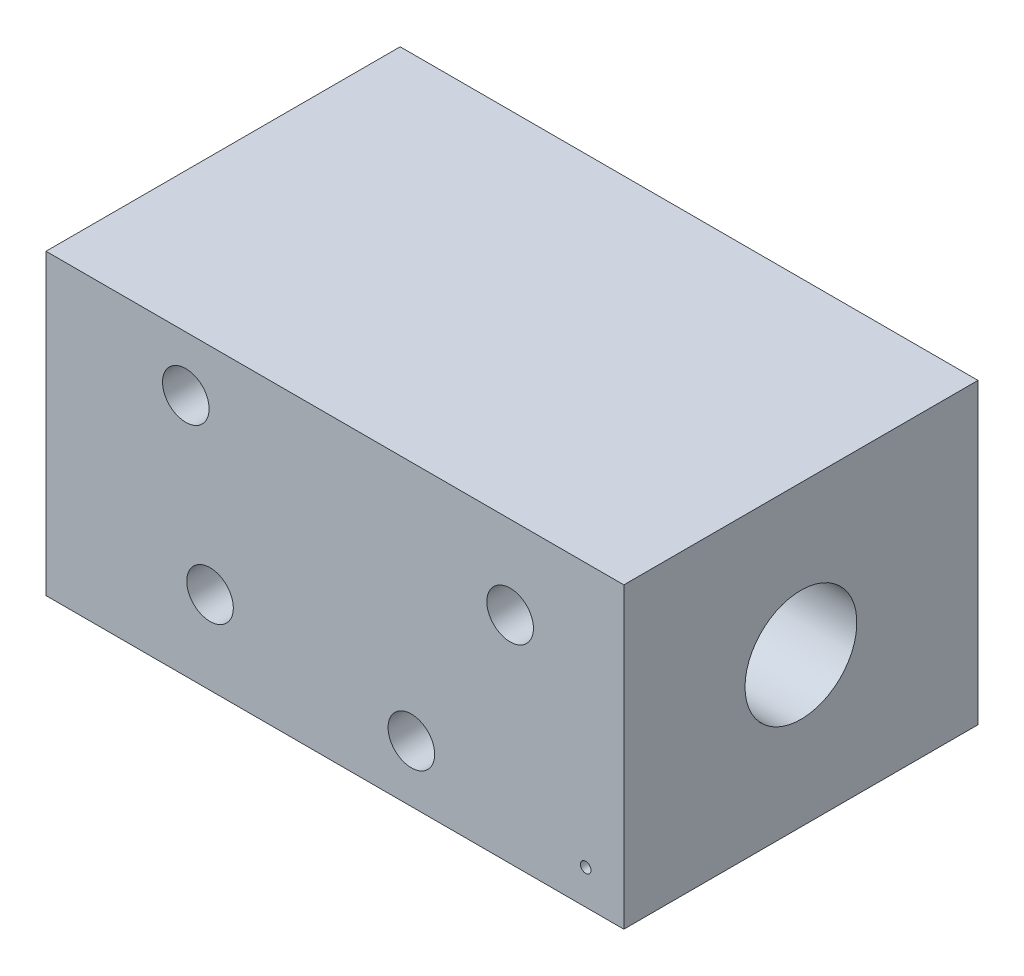
SolidWorks part; units mm, degrees
ref_plane "Front Plane" through (0, 0, 0) normal (0, 0, 1) x (1, 0, 0)
ref_plane "Top Plane" through (0, 0, 0) normal (0, 1, 0) x (1, 0, 0)
ref_plane "Right Plane" through (0, 0, 0) normal (1, 0, 0) x (0, 0, -1)
sketch "Sketch1" plane through (0, 0, 0) normal (0, 1, 0) x (1, 0, 0)
  line L1 (-15.5, -9.5) -> (15.5, -9.5)
  line L2 (-15.5, -9.5) -> (-15.5, 9.5)
  line L3 (-15.5, 9.5) -> (15.5, 9.5)
  line L4 (15.5, -9.5) -> (15.5, 9.5)
  line L5 (-15.5, -9.5) -> (15.5, 9.5) construction
  line L6 (-15.5, 9.5) -> (15.5, -9.5) construction
  point P0 (0, 0)
  dimension "D1" = 31
  dimension "D2" = 19
extrude "Boss-Extrude1" add sketch "Sketch1" along normal blind 16
sketch "Sketch3" plane through (0, 0, 9.5) normal (0, 0, 1) x (1, 0, 0)
  line L0 (15.5, 16) -> (15.5, 0) construction
  line L1 (0, 16) -> (0, 0) construction
  line L2 (-15.5, 16) -> (15.5, 16) construction
  line L3 (-15.5, 8) -> (15.5, 8) construction
  line L4 (-15.5, 16) -> (-15.5, 0) construction
  line L5 (-15.5, 0) -> (15.5, 0) construction
  circle A12 centre (13.4531, 1.8556) radius 0.2814
  circle A13 centre (9.4, 11.55) radius 1.25
  circle A14 centre (4.1, 3.05) radius 1.25
  circle A15 centre (-6.7, 4.45) radius 1.25
  circle A16 centre (-8, 13.05) radius 1.25
extrude "Cut-Extrude1" cut sketch "Sketch3" against normal blind 2
sketch "Sketch7" plane through (-15.5, 0, 0) normal (-1, 0, 0) x (0, 0, 1)
  line L0 (-9.5, 16) -> (9.5, 0) construction
  circle A0 centre (0, 8) radius 3
  point P6 (0, 8)
  dimension "D1" = 6
extrude "Cut-Extrude2" cut sketch "Sketch7" against normal through all
